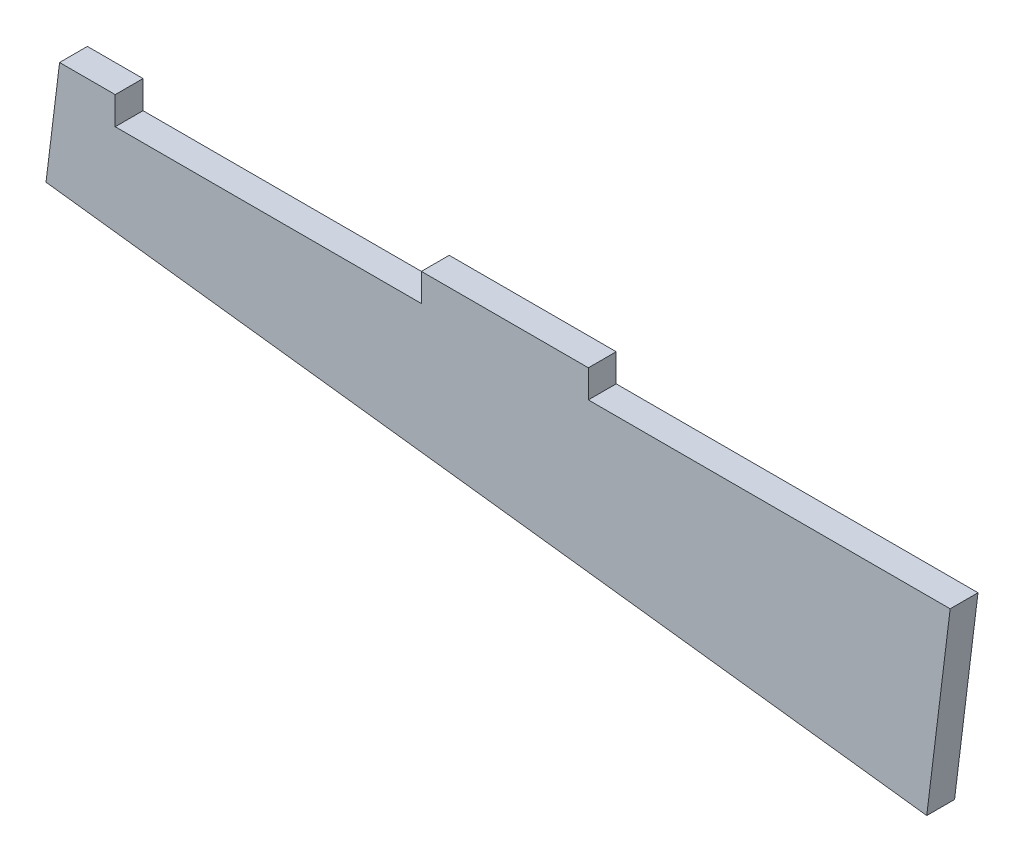
SolidWorks part; units mm, degrees
ref_plane "Front Plane" through (0, 0, 0) normal (0, 0, 1) x (1, 0, 0)
ref_plane "Top Plane" through (0, 0, 0) normal (0, 1, 0) x (1, 0, 0)
ref_plane "Right Plane" through (0, 0, 0) normal (1, 0, 0) x (0, 0, -1)
sketch "Sketch1" plane through (0, 0, 0) normal (0, 0, 1) x (1, 0, 0)
  line L0 (-195.3168, -62.6592) -> (-182.6168, -62.6592)
  line L4 (-182.6168, -62.6592) -> (-182.6168, -69.0092)
  line L5 (-182.6168, -69.0092) -> (-112.7668, -69.0092)
  line L6 (-112.7668, -69.0092) -> (-112.7668, -62.6592)
  line L7 (-112.7668, -62.6592) -> (-74.6668, -62.6592)
  line L8 (-74.6668, -62.6592) -> (-74.6668, -69.0092)
  line L9 (-74.6668, -69.0092) -> (7.8832, -69.0092)
  line L10 (7.8832, -69.0092) -> (2.5379, -112.5435)
  line L11 (2.5379, -112.5435) -> (-198.4122, -87.8699)
  line L12 (-198.4122, -87.8699) -> (-195.3168, -62.6592)
  line L13 (-1124.7791, 73.1794) -> (-1105.8711, 70.8577) construction
  dimension "D1" = 12.7
  dimension "D2" = 6.35
  dimension "D3" = 69.85
  dimension "D4" = 38.1
  dimension "D5" = 82.55
  dimension "D6" = 25.4
extrude "Boss-Extrude1" add sketch "Sketch1" against normal blind 6.35
